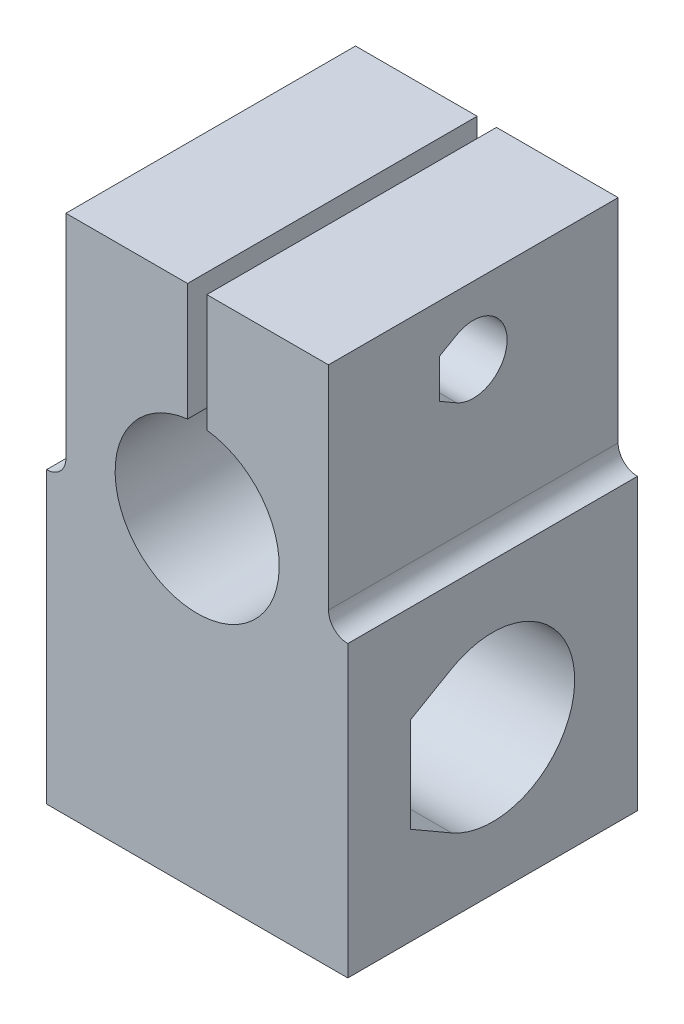
SolidWorks part; units mm, degrees
ref_plane "Piano frontale" through (0, 0, 0) normal (0, 0, 1) x (1, 0, 0)
ref_plane "Piano superiore" through (0, 0, 0) normal (0, 1, 0) x (1, 0, 0)
ref_plane "Piano destro" through (0, 0, 0) normal (1, 0, 0) x (0, 0, -1)
sketch "Schizzo1" plane through (0, 0, 0) normal (0, 0, 1) x (1, 0, 0)
  line L0 (-7.8, 0) -> (-7.8, 15)
  line L1 (-7.8, 15) -> (-6.8, 15)
  line L2 (-6.8, 15) -> (-6.8, 27)
  line L3 (-6.8, 27) -> (-0.5, 27)
  line L4 (-0.5, 27) -> (-0.5, 20.9205)
  line L5 (0.5, 27) -> (0.5, 20.9205)
  line L6 (0.5, 27) -> (6.8, 27)
  line L7 (6.8, 27) -> (6.8, 15)
  line L8 (6.8, 15) -> (7.8, 15)
  line L9 (7.8, 15) -> (7.8, 0)
  line L10 (7.8, 0) -> (-7.8, 0)
  line L11 (0, 0) -> (0, 37.7654) construction
  line L12 (-7.8, 7.5) -> (7.8, 7.5) construction
  arc A62 (-0.5, 20.9205) -> (0.5, 20.9205) centre (0, 16.7) ccw
  dimension "D3" = 8.5
  dimension "D5" = 12
  dimension "D8" = 9.2
  dimension "D1" = 15
  dimension "D2" = 1
  dimension "D6" = 15.6
  dimension "D7" = 1
extrude "Main body" add sketch "Schizzo1" along normal mid plane 15 contours L5 A62 L4 L3 L2 L1 L0 L10 L9 L8 L7 L6
sketch "Schizzo2" plane through (6.8, 0, 0) normal (1, 0, 0) x (0, 0, -1)
  line L0 (-7.5, 27) -> (7.5, 27) construction
  line L1 (-7.5, 27) -> (7.5, 27)
  line L2 (0, 27) -> (0, 23.5) construction
  line L3 (-1.75, 22.4896) -> (-1.75, 24.5104)
  line L4 (-1.75, 24.5104) -> (-0.875, 25.0155)
  line L5 (-1.75, 22.4896) -> (-0.875, 21.9845)
  arc A0 (-0.875, 21.9845) -> (-0.875, 25.0155) centre (0, 23.5) ccw
  point P9 (-1.75, 23.5)
  dimension "D1" = 3.5
  dimension "D2" = 120
  dimension "D3" = 3.5
extrude "Screw" cut sketch "Schizzo2" against normal through all both and the other way through all contours A0 L4 L3 L5
sketch "Schizzo6" plane through (-6.8, 0, 0) normal (-1, 0, 0) x (0, 0, 1)
  line L1 (3.25, 23.5) -> (1.625, 26.3146)
  line L2 (1.625, 26.3146) -> (-1.625, 26.3146)
  line L3 (-1.625, 26.3146) -> (-3.25, 23.5)
  line L4 (-3.25, 23.5) -> (-1.625, 20.6854)
  line L5 (-1.625, 20.6854) -> (1.625, 20.6854)
  line L6 (1.625, 20.6854) -> (3.25, 23.5)
  circle A0 centre (0, 23.5) radius 2.8146 construction
  dimension "D1" = 6.5
extrude "Nut recess" cut sketch "Schizzo6" against normal blind 2.4
sketch "Schizzo7" plane through (-7.8, 0, 0) normal (-1, 0, 0) x (0, 0, 1)
  line L0 (-7.5, 15) -> (7.5, 0) construction
  line L1 (4.25, 5.0463) -> (4.25, 9.9537)
  line L2 (4.25, 9.9537) -> (2.125, 11.1806)
  line L3 (4.25, 5.0463) -> (2.125, 3.8194)
  arc A0 (2.125, 11.1806) -> (2.125, 3.8194) centre (0, 7.5) ccw
  point P5 (0, 0)
  point P9 (4.25, 7.5)
  dimension "D1" = 8.5
extrude "Bar hole" cut sketch "Schizzo7" against normal through all
sketch "Schizzo8" plane through (0, 0, -7.5) normal (0, 0, -1) x (-1, 0, 0)
  line L0 (0, 12.45) -> (-0.5389, 12.9889)
  line L1 (3.0052, 13.6948) -> (-3.0052, 19.7052) construction
  line L2 (-0.5, 20.9205) -> (-0.5, 20.4165)
  line L3 (0.5, 20.9205) -> (0.5, 20.4165)
  line L4 (-4.25, 16.7) -> (-3.7111, 17.2389)
  line L5 (-4.25, 16.7) -> (4.25, 16.7) construction
  line L6 (0, 12.45) -> (0, 20.4165) construction
  line L7 (-4.25, 16.7) -> (-3.7111, 16.1611)
  line L8 (4.25, 16.7) -> (3.7111, 16.1611)
  line L9 (4.25, 16.7) -> (3.7111, 17.2389)
  line L10 (0, 12.45) -> (0.5389, 12.9889)
  line L11 (3.0052, 19.7052) -> (-3.0052, 13.6948) construction
  line L12 (3.0052, 13.6948) -> (3.0052, 14.457)
  line L13 (-3.0052, 13.6948) -> (-3.0052, 14.457)
  line L14 (3.0052, 13.6948) -> (2.243, 13.6948)
  line L15 (-3.0052, 19.7052) -> (-2.243, 19.7052)
  line L16 (-3.0052, 19.7052) -> (-3.0052, 18.943)
  line L17 (-3.0052, 13.6948) -> (-2.243, 13.6948)
  line L18 (3.0052, 19.7052) -> (2.243, 19.7052)
  line L19 (3.0052, 19.7052) -> (3.0052, 18.943)
  arc A0 (-0.5, 20.9205) -> (0.5, 20.9205) centre (0, 16.7) ccw construction
  arc A1 (-0.5, 20.9205) -> (0.5, 20.9205) centre (0, 16.7) ccw
  arc A2 (-0.5, 20.4165) -> (-2.243, 19.7052) centre (0, 16.7) ccw
  arc A3 (-3.7111, 16.1611) -> (-3.0052, 14.457) centre (0, 16.7) ccw
  arc A4 (0.5389, 12.9889) -> (2.243, 13.6948) centre (0, 16.7) ccw
  arc A5 (3.7111, 17.2389) -> (3.0052, 18.943) centre (0, 16.7) ccw
  arc A6 (3.0052, 14.457) -> (3.7111, 16.1611) centre (0, 16.7) ccw
  arc A7 (-3.0052, 18.943) -> (-3.7111, 17.2389) centre (0, 16.7) ccw
  arc A8 (2.243, 19.7052) -> (0.5, 20.4165) centre (0, 16.7) ccw
  arc A9 (-2.243, 13.6948) -> (-0.5389, 12.9889) centre (0, 16.7) ccw
  point P21 (0, 16.7)
  arc M12 (0.5, 20.9205) -> (-0.5, 20.9205) centre (0, 16.7) cw
  dimension "D1" = 3.75
  dimension "D2" = 45
  dimension "D3" = 45
  dimension "D5" = 45
  dimension "D6" = 45
extrude "Rod stop" add sketch "Schizzo8" against normal blind 1 contours A3 L7 L0 M12 | A2 L2 L4 M12 | A5 L9 L3 M12 | A4 L10 L8 M12 | A6 L12 L8 M12 | A9 L17 L0 M12 | A7 L16 L4 M12 | A8 L18 L3 M12 region at (1.5109, 13.0524, -7.5) region at (-1.6294, 20.3042, -7.5) region at (-3.6476, 18.2109, -7.5) region at (-3.6476, 15.1891, -7.5) region at (1.6294, 20.3042, -7.5) region at (3.6476, 18.2109, -7.5) region at (3.6476, 15.1891, -7.5) region at (-1.5109, 13.0524, -7.5)
fillet "Relief 1" radius 1 1 edges at (6.8, 15, 0)
fillet "Relief 2" radius 1 1 edges at (-6.8, 15, 0)
ref_axis "Bar axis" through (7.8, 7.5, 0) along (-1, 0, 0)
ref_axis "Rod axis" through (0, 16.7, 7.5) along (0, 0, -1)
ref_axis "Rod clamp axis" through (0.5, 23.5, 0) along (1, 0, 0)
